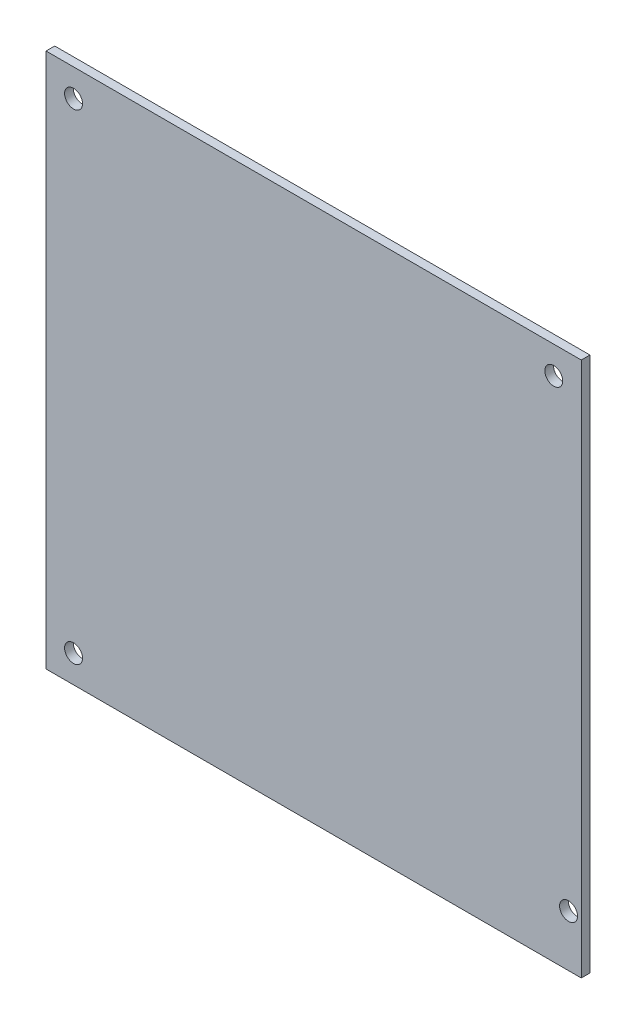
SolidWorks part; units mm, degrees
material "FR4"
ref_plane "Front Plane" through (0, 0, 0) normal (0, 0, 1) x (1, 0, 0)
ref_plane "Top Plane" through (0, 0, 0) normal (0, 1, 0) x (1, 0, 0)
ref_plane "Right Plane" through (0, 0, 0) normal (1, 0, 0) x (0, 0, -1)
sketch "Sketch1" plane through (0, 0, 0) normal (0, 0, 1) x (1, 0, 0)
  line L1 (46.25, -46.25) -> (-46.25, -46.25)
  line L2 (46.25, -46.25) -> (46.25, 46.25)
  line L3 (46.25, 46.25) -> (-46.25, 46.25)
  line L4 (-46.25, -46.25) -> (-46.25, 46.25)
  line L5 (46.25, -46.25) -> (-46.25, 46.25) construction
  line L6 (46.25, 46.25) -> (-46.25, -46.25) construction
  point P0 (0, 0)
  dimension "D1" = 92.5
  dimension "D2" = 92.5
extrude "Boss-Extrude1" add sketch "Sketch1" along normal blind 1.5
hole_wizard "Ø3.1 (3.1) Diameter Hole1" positions "Sketch3" profile "Sketch2" hole size "Ø3.1" standard "ANSI Metric" end condition through all
sketch "Sketch3" plane through (0, 0, 1.5) normal (0, 0, 1) x (1, 0, 0)
  line L0 (46.25, -46.25) -> (46.25, 46.25) construction
  line L1 (-46.25, -46.25) -> (46.25, -46.25) construction
  point P0 (-41.5, 41.5)
  point P2 (41.5, 41.5)
  point P4 (44.05, -37.33)
  point P6 (-41.5, -41.5)
  dimension "D1" = 2.2
  dimension "D2" = 8.92
sketch "Sketch2" plane through (-41.5, 41.5, 1.5) normal (1, 0, 0) x (0, -1, 0)
  line L0 (0, 0) -> (0, 1.5)
  line L1 (0, 1.5) -> (1.55, 1.5)
  line L2 (1.55, 1.5) -> (1.55, 0)
  line L5 (1.55, 0) -> (0, 0)
  line L11 (0, -6.35) -> (0, 107.95) construction
  dimension "Thru Hole Dia." = 3.1
  dimension "Thru Hole Depth" = 1.5
